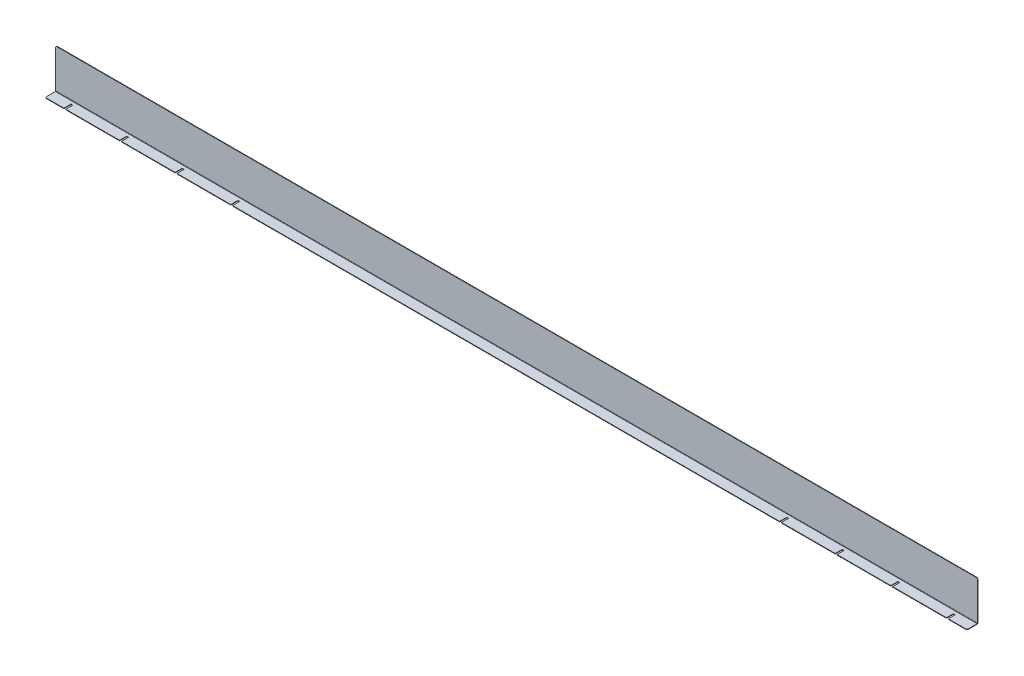
SolidWorks part; units mm, degrees
note: The reader was unsure of these and kept them because the rebuilt part matched: bend radius of "BaseBend4".
material "AISI 304"
ref_plane "Front Plane" through (0, 0, 0) normal (0, 0, 1) x (1, 0, 0)
ref_plane "Top Plane" through (0, 0, 0) normal (0, 1, 0) x (1, 0, 0)
ref_plane "Right Plane" through (0, 0, 0) normal (1, 0, 0) x (0, 0, -1)
sketch "Sketch1" plane through (0, 0, 0) normal (1, 0, 0) x (0, 0, -1)
  line L0 (0, 0) -> (0, 150)
  line L4 (0, 0) -> (-40, 0)
  dimension "D1" = 150
  dimension "D5" = 40
base flange "Base-Flange1" sketch "Sketch1" end condition mid plane depth 3522 reverse direction no thickness 2 reverse thickness direction no bend radius 1.3
bend "BaseBend4" bend radius 1.3 bend angle 90 parameters "D5"=7
fillet "Fillet1" radius 5 4 edges at (1761, 150, -1) (1761, -1, 40) (-1761, -1, 40) (-1761, 150, -1)
sketch "Sketch2" plane through (0, 0, 0) normal (0, 1, 0) x (1, 0, 0)
  line L0 (1756, 2) -> (-1756, 2) construction
  line L2 (-1682.5, -48) -> (-1689.5, -48)
  line L3 (-1761, -35) -> (-1761, -1.3) construction
  line L6 (-1682.5, -48) -> (-1682.5, -13)
  line L21 (-1682.5, -13) -> (-1689.5, -13)
  line L22 (-1689.5, -48) -> (-1689.5, -13)
  line L23 (-1682.5, -48) -> (-1689.5, -13) construction
  line L24 (-1682.5, -13) -> (-1689.5, -48) construction
  point P41 (-1686, -30.5)
  dimension "D1" = 15
  dimension "D2" = 75
  dimension "D7" = 7
  dimension "D8" = 35
extrude "Cut-Extrude1" cut sketch "Sketch2" against normal blind 10
pattern_linear "阵列(线性)1" count 4 spacing 212.51 along (1, 0, 0) of "Cut-Extrude1"
ref_plane "基准面1" through (0, 0, 0) normal (-1, 0, 0) x (0, 0, 1)
mirror "镜向1" about plane through (0, 0, 0) normal (-1, 0, 0) of "阵列(线性)1", "Cut-Extrude1"
sketch "Bend-Lines1" [suppressed] plane through (0, 0, 0) normal (0, 1, 0) x (1, 0, 0)
sketch "Bounding-Box1" [suppressed] plane through (0, 0, 0) normal (0, 1, 0) x (1, 0, 0)
sheet metal parameters "Sheet-Metal1" thickness 2 parameters "D1"=2
flat pattern "Flat-Pattern1" [suppressed]
sketch "Bend-Lines2" plane through (0, 0, 0) normal (0, 0, 1) x (1, 0, 0)
  line L6 (500, -0.3423) -> (-500, -0.3423) construction
  line L7 (500, -0.3423) -> (-500, -0.3423) construction
sketch3d "Bounding-Box2" [suppressed]
  line L0 (-1000, 25.0001, 0) -> (0, 25, 0) construction
  line L1 (-1000, -43.6845, 0) -> (0, -43.6845, 0) construction
  line L2 (-1000, 25.0001, 0) -> (-1000, -43.6845, 0) construction
  line L3 (0, 25, 0) -> (0, -43.6845, 0) construction
bend of the flat pattern "Flatten-<BaseBend4>1"
sheet metal parameters "Sheet-Metal2" thickness 2 parameters "D1"=2
flat pattern "Flat-Pattern1"
sketch "Bend-Lines2" plane through (0, 0, 0) normal (0, 0, 1) x (1, 0, 0)
  line L6 (2373.5, -0.3423) -> (-2373.5, -0.3423) construction
  line L7 (2373.5, -0.3423) -> (-2373.5, -0.3423) construction
sketch3d "Bounding-Box2" [suppressed]
  line L0 (-4747, 150.0004, 0) -> (0, 150, 0) construction
  line L1 (-4747, -40.6842, 0) -> (0, -40.6845, 0) construction
  line L2 (-4747, 150.0004, 0) -> (-4747, -40.6842, 0) construction
  line L3 (0, 150, 0) -> (0, -40.6845, 0) construction
bend of the flat pattern "Flatten-<BaseBend4>1"
sheet metal parameters "钣金3" thickness 2 parameters "D1"=2
flat pattern "Flat-Pattern1"
sketch "Bend-Lines2" plane through (0, 0, 0) normal (0, 0, 1) x (1, 0, 0)
  line L6 (4746.75, -0.3423) -> (-4746.75, -0.3423) construction
  line L7 (4746.75, -0.3423) -> (-4746.75, -0.3423) construction
sketch3d "Bounding-Box2" [suppressed]
  line L0 (-9493.5, 150.0007, 0) -> (0, 150, 0) construction
  line L1 (-9493.5, -40.6838, 0) -> (0, -40.6845, 0) construction
  line L2 (-9493.5, 150.0007, 0) -> (-9493.5, -40.6838, 0) construction
  line L3 (0, 150, 0) -> (0, -40.6845, 0) construction
bend of the flat pattern "Flatten-<BaseBend4>1"
sheet metal parameters "钣金4" thickness 2 parameters "D1"=2
flat pattern "Flat-Pattern1"
sketch "Bend-Lines2" plane through (0, 0, 0) normal (0, 0, 1) x (1, 0, 0)
  line L6 (1761, -0.3423) -> (-1761, -0.3423) construction
  line L7 (1761, -0.3423) -> (-1761, -0.3423) construction
sketch3d "Bounding-Box2" [suppressed]
  line L0 (-3522, 150.0003, 0) -> (0, 150, 0) construction
  line L1 (-3522, -40.6843, 0) -> (0, -40.6845, 0) construction
  line L2 (-3522, 150.0003, 0) -> (-3522, -40.6843, 0) construction
  line L3 (0, 150, 0) -> (0, -40.6845, 0) construction
bend of the flat pattern "Flatten-<BaseBend4>1"
